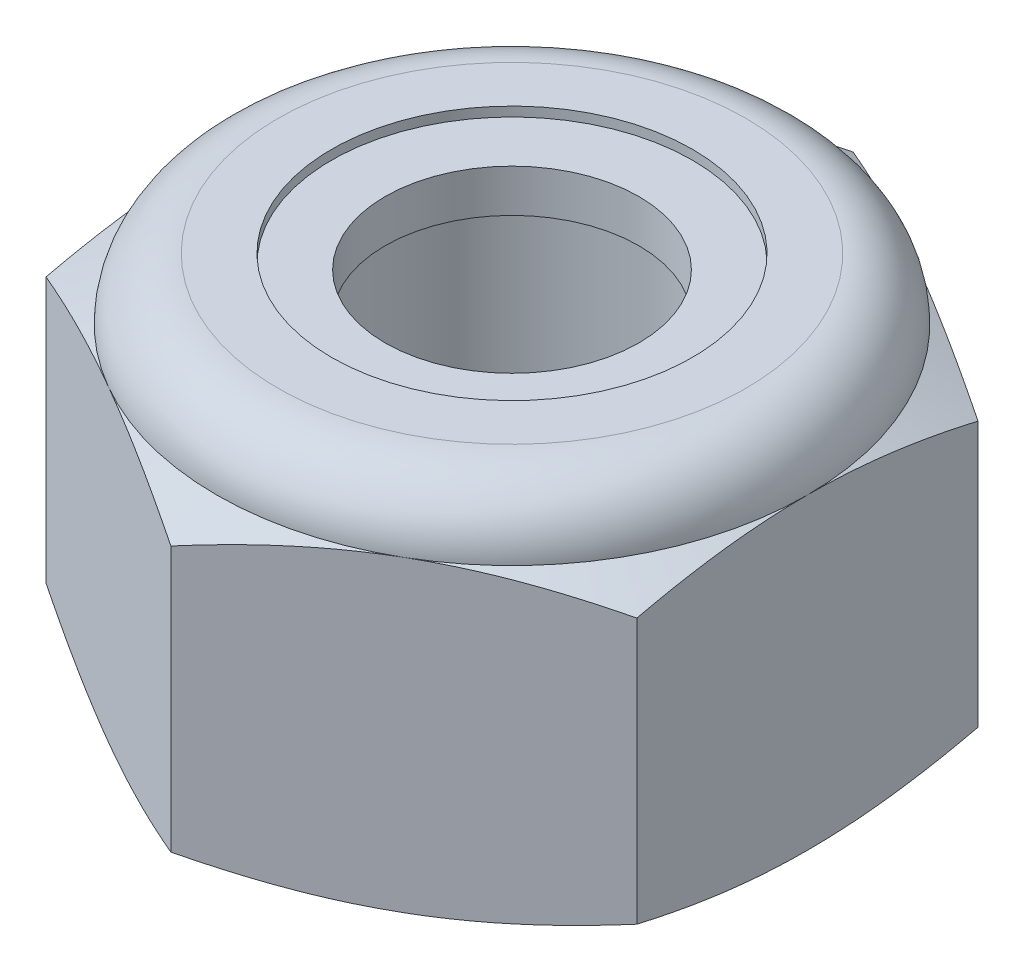
SolidWorks part; units mm, degrees
material "Plain Carbon Steel"
ref_plane "Front" through (0, 0, 0) normal (0, 0, 1) x (1, 0, 0)
ref_plane "Top" through (0, 0, 0) normal (0, 1, 0) x (1, 0, 0)
ref_plane "Right" through (0, 0, 0) normal (1, 0, 0) x (0, 0, -1)
sketch "Sketch1" plane through (0, 0, 0) normal (0, 1, 0) x (1, 0, 0)
  line L1 (0, 5.4993) -> (-4.7625, 2.7496)
  line L2 (-4.7625, 2.7496) -> (-4.7625, -2.7496)
  line L3 (-4.7625, -2.7496) -> (0, -5.4993)
  line L4 (0, -5.4993) -> (4.7625, -2.7496)
  line L5 (4.7625, -2.7496) -> (4.7625, 2.7496)
  line L6 (4.7625, 2.7496) -> (0, 5.4993)
  circle A0 centre (0, 0) radius 4.7625 construction
  dimension "Hex Flats" = 9.525
extrude "Extrude1" add sketch "Sketch1" along normal blind 5.9531
sketch "Sketch2" plane through (0, 0, 0) normal (1, 0, 0) x (0, 0, -1)
  line L0 (-2.413, 0) -> (-2.413, 5.9531) construction
  line L1 (0, 0) -> (2.413, 0)
  line L2 (0, 0) -> (0, 5.9531)
  line L3 (0, 5.9531) -> (2.413, 5.9531)
  line L4 (2.413, 0) -> (2.413, 5.9531)
  line L5 (-2.7496, 5.9531) -> (2.7496, 5.9531) construction
  line L7 (0, -2.413) -> (0, 0) construction
  dimension "Thread Dia" = 4.826
revolve "Revolve1" add sketch "Sketch2" angle 360 about L7
sketch "Sketch3" plane through (0, 0, 0) normal (1, 0, 0) x (0, 0, -1)
  line L0 (2.413, 5.9531) -> (-2.413, 5.9531) construction
  line L1 (-2.413, 5.9531) -> (-2.413, 5.1594) construction
  line L2 (-2.413, 5.1594) -> (2.413, 5.9531) construction
  line L3 (2.413, 5.9531) -> (2.4291, 5.8552) construction
  line L4 (2.4291, 5.8552) -> (2.5418, 5.1699)
  line L5 (2.5418, 5.1699) -> (2.0776, 5.3449)
  line L6 (2.0776, 5.3449) -> (2.0454, 5.5407)
  line L7 (2.0454, 5.5407) -> (2.4291, 5.8552)
  line L8 (2.0615, 5.4428) -> (2.4855, 5.5126) construction
  line L9 (2.413, 5.9531) -> (2.413, 5.5006) construction
  line L10 (2.413, 5.5006) -> (-2.413, 4.7069) construction
  line L11 (-2.413, 4.7069) -> (-2.413, 5.1594) construction
  line L12 (-0.1397, 5.9531) -> (0.1397, 4.2544) construction
  line L13 (-2.413, 0) -> (-2.413, 5.9531) construction
  line L14 (0, 5.9531) -> (2.413, 5.9531) construction
  line L15 (2.413, 0) -> (2.413, 5.9531) construction
  point P13 (0, 5.1038)
  dimension "D4" = 60
sketch "Sketch4" plane through (0, 0, 0) normal (1, 0, 0) x (0, 0, -1)
  line L0 (0, 5.9531) -> (2.413, 5.9531)
  line L1 (2.413, 5.9531) -> (2.0454, 5.7817)
  line L2 (2.0454, 5.7817) -> (2.0454, 0.1714)
  line L3 (2.0454, 0.1714) -> (2.413, 0)
  line L4 (2.413, 0) -> (0, 0)
  line L5 (0, 0) -> (0, 5.9531)
  line L6 (2.413, 0) -> (2.413, 5.9531) construction
  line L7 (0, 5.9531) -> (2.413, 5.9531) construction
  line L8 (0, 0) -> (2.413, 0) construction
  line L9 (0, 0) -> (0, 5.9531) construction
  line L10 (0, 5.9531) -> (0, 6.3587) construction
  dimension "D1" = 25
combine bodies "Combine1" operation type subtract main body 108 bodies to subtract 109
sketch "Sketch5" plane through (0, 0, 0) normal (1, 0, 0) x (0, 0, -1)
  line L0 (0, 0) -> (4.7625, 0)
  line L1 (4.7625, 0) -> (5.4993, 0.3436)
  line L2 (5.4993, 0.3436) -> (5.4993, 4.6174)
  line L3 (5.4993, 4.6174) -> (4.7625, 4.9609)
  line L4 (3.7703, 5.9531) -> (3.7703, 7.2231)
  line L5 (3.7703, 7.2231) -> (6.7693, 7.2231)
  line L6 (6.7693, 7.2231) -> (6.7693, -1.27)
  line L7 (6.7693, -1.27) -> (0, -1.27)
  line L8 (0, -1.27) -> (0, 0)
  line L9 (4.7625, 4.9609) -> (4.7625, 0) construction
  line L10 (0, 0) -> (2.413, 0) construction
  line L13 (5.4993, 2.4805) -> (6.7693, 2.4805) construction
  line L14 (5.4993, 5.9531) -> (5.4993, 0) construction
  line L15 (0, 0) -> (0, 7.2231) construction
  line L20 (0, 7.2231) -> (3.7703, 7.2231) construction
  line L22 (0, 5.9531) -> (2.413, 5.9531) construction
  arc A0 (4.7625, 4.9609) -> (3.7703, 5.9531) centre (3.7703, 4.9609) ccw
  dimension "D1" = 25
  dimension "D2" = 1.27
revolve "Cut-Revolve3" cut sketch "Sketch5" angle 360 about L15
sketch "Sketch6" plane through (0, 0, 0) normal (1, 0, 0) x (0, 0, -1)
  line L0 (0, 4.9609) -> (4.6101, 4.9609)
  line L1 (3.7703, 5.8007) -> (2.9079, 5.8007)
  line L2 (0, 7.2231) -> (0, 4.9609)
  line L3 (2.9079, 7.2231) -> (0, 7.2231)
  line L4 (0, 7.2231) -> (3.7703, 7.2231) construction
  line L5 (0, 0) -> (0, 7.2231) construction
  line L6 (0, 7.2231) -> (0, 44.323) construction
  line L7 (2.9079, 5.8007) -> (2.9079, 7.2231)
  line L8 (3.7703, 5.9531) -> (3.7703, 5.8007) construction
  line L9 (2.9079, 5.8007) -> (2.0454, 5.8007) construction
  line L10 (2.0454, 5.8007) -> (2.0454, 5.7817) construction
  arc A0 (4.6101, 4.9609) -> (3.7703, 5.8007) centre (3.7703, 4.9609) ccw
  arc A1 (4.7625, 4.9609) -> (3.7703, 5.9531) centre (3.7703, 4.9609) ccw construction
  dimension "D1" = 0.1524
revolve "Cut-Revolve4" cut sketch "Sketch6" angle 360 about L6
sketch "Sketch7" plane through (0, 0, 0) normal (1, 0, 0) x (0, 0, -1)
  line L0 (2.0454, 5.0371) -> (4.5301, 5.0371)
  line L1 (3.7703, 5.7245) -> (2.0454, 5.7245)
  line L2 (2.0454, 5.7245) -> (2.0454, 5.0371)
  line L3 (2.0454, 5.0371) -> (0, 5.0371) construction
  line L4 (0, 5.0371) -> (0, 5.7245) construction
  line L5 (0, 5.7245) -> (2.0454, 5.7245) construction
  line L6 (2.0454, 5.0371) -> (2.0454, 4.9609) construction
  line L7 (0, 4.9609) -> (4.6101, 4.9609) construction
  line L8 (3.7703, 5.7245) -> (3.7703, 5.8007) construction
  arc A0 (4.5301, 5.0371) -> (3.7703, 5.7245) centre (3.7703, 4.9609) ccw
  arc A2 (4.6101, 4.9609) -> (3.7703, 5.8007) centre (3.7703, 4.9609) ccw construction
  dimension "D1" = 0.0762
revolve "Revolve2" add sketch "Sketch7" angle 360 about L4
ref_axis "Axis1" through (0, 0, 0) along (0, 1, 0)
equation "\"D1@Sketch3\"=\"Thread Pitch@Sketch3\"/8"
equation "\"D2@Sketch3\"=\"Thread Pitch@Sketch3\"/4"
equation "\"D5@Sketch3\"=\"Thread Pitch@Sketch3\""
equation "\"D4@Sketch5\"=\"Height@Extrude1\"/6"
